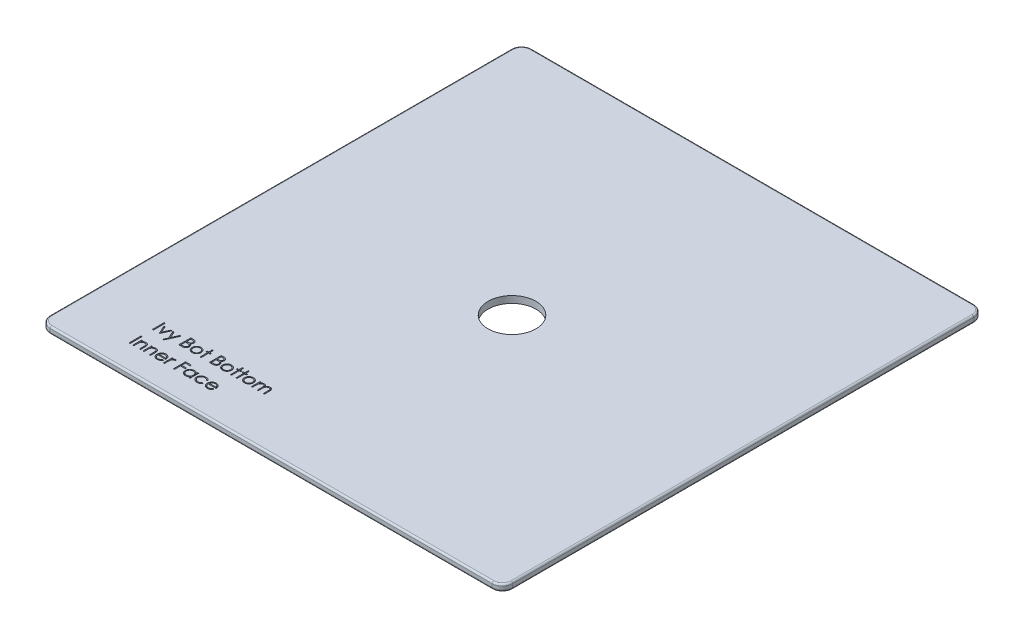
SolidWorks part; units mm, degrees
ref_plane "Front Plane" through (0, 0, 0) normal (0, 0, 1) x (1, 0, 0)
ref_plane "Top Plane" through (0, 0, 0) normal (0, 1, 0) x (1, 0, 0)
ref_plane "Right Plane" through (0, 0, 0) normal (1, 0, 0) x (0, 0, -1)
sketch "Sketch1" plane through (0, 0, 0) normal (0, 1, 0) x (1, 0, 0)
  line L1 (-67.7, 70.5) -> (67.7, 70.5)
  line L2 (-67.7, 70.5) -> (-67.7, -70.5)
  line L3 (-67.7, -70.5) -> (67.7, -70.5)
  line L4 (67.7, 70.5) -> (67.7, -70.5)
  point P4 (0, -70.5)
  point P6 (-67.7, 0)
  dimension "D1" = 135.4
  dimension "D2" = 141
extrude "Boss-Extrude1" add sketch "Sketch1" along normal blind 2 contours L1 L4 L3 L2
sketch "Sketch6" plane through (0, 2, 0) normal (0, 1, 0) x (1, 0, 0)
  circle A0 centre (0, 0) radius 7
  dimension "D1" = 14
extrude "Cut-Extrude1" cut sketch "Sketch6" against normal through all contours A0
fillet "Fillet1" radius 0.5 8 edges at (-67.7, 0, 0) (0, 0, -70.5) (0, 0, 70.5) (67.7, 0, 0) (67.7, 2, 0) (-67.7, 2, 0) (0, 2, 70.5) (0, 2, -70.5)
sketch "Sketch9" plane through (0, 2, 0) normal (0, 1, 0) x (1, 0, 0)
  text T0 "Ivy Bot Bottom\r\nInner Face"
extrude "Cut-Extrude4" cut sketch "Sketch9" against normal blind 1
sketch "Sketch10" plane through (0, 0, 0) normal (0, -1, 0) x (1, 0, 0)
  line L0 (-12.9733, 25) -> (12.9733, 25) construction
  line L1 (-12.9733, -25) -> (12.9733, -25) construction
  text T0 "3               1"
  text T1 " 2               4"
  point P8 (0, 25)
  point P12 (0, -25)
  dimension "D1" = 25
  dimension "D2" = 25
extrude "Cut-Extrude5" cut sketch "Sketch10" against normal blind 1
sketch "Sketch11" plane through (0, 0, 0) normal (0, -1, 0) x (1, 0, 0)
  line L0 (0, 70) -> (0, -70) construction
  line L1 (67.2, 70) -> (-67.2, 70) construction
  line L2 (-67.2, -70) -> (67.2, -70) construction
  line L3 (-67.2, 0) -> (67.2, 0) construction
  line L4 (67.2, -70) -> (67.2, 70) construction
  line L5 (50, 0) -> (-50, 0) construction
  circle A0 centre (-50, 0) radius 2.5
  circle A1 centre (50, 0) radius 2.5
  point P13 (0, 0)
  point P17 (0, 0)
extrude "Boss-Extrude2" add sketch "Sketch11" along normal blind 10
fillet "Fillet4" radius 2 2 edges at (50, -10, 2.5) (-50, -10, -2.5)
fillet "Fillet5" radius 3 12 edges at (67.5536, 0.1464, 70.3536) (67.5536, 1.8536, 70.3536) (67.7, 1, 70.5) (67.5536, 0.1464, -70.3536) (67.5536, 1.8536, -70.3536) (67.7, 1, -70.5) (-67.5536, 0.1464, 70.3536) (-67.5536, 0.1464, -70.3536) (-67.5536, 1.8536, -70.3536) (-67.5536, 1.8536, 70.3536) (-67.7, 1, 70.5) (-67.7, 1, -70.5)
